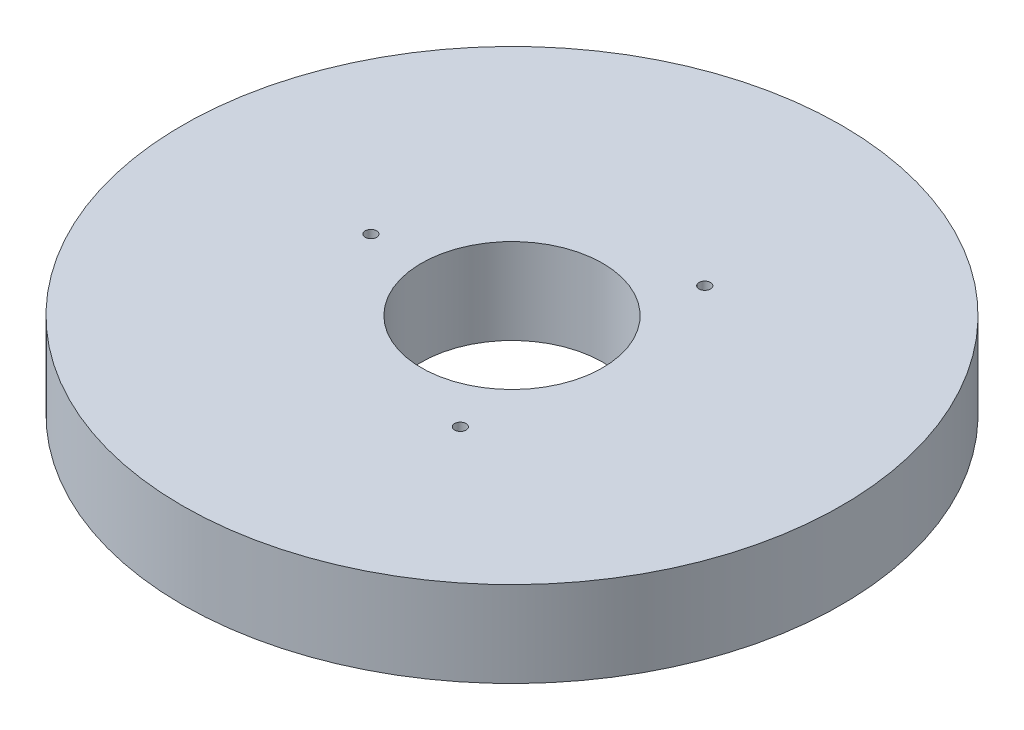
SolidWorks part; units mm, degrees
ref_plane "Front Plane" through (0, 0, 0) normal (0, 0, 1) x (1, 0, 0)
ref_plane "Top Plane" through (0, 0, 0) normal (0, 1, 0) x (1, 0, 0)
ref_plane "Right Plane" through (0, 0, 0) normal (1, 0, 0) x (0, 0, -1)
sketch "Sketch1" plane through (0, 0, 0) normal (0, 1, 0) x (1, 0, 0)
  circle A0 centre (0, 0) radius 100
  dimension "FLANGE_OD" = 200
extrude "Boss-Extrude1" add sketch "Sketch1" along normal blind 26
sketch "Sketch2" plane through (0, 0, 0) normal (0, 1, 0) x (1, 0, 0)
  circle A0 centre (0, 0) radius 27.5
  dimension "BORE_D" = 55
extrude "Cut-Extrude1" cut sketch "Sketch2" along normal through all
sketch "Sketch3" plane through (0, 26, 0) normal (0, 1, 0) x (1, 0, 0)
  circle A0 centre (0, 0) radius 42.8122 construction
  circle A1 centre (-42.8122, 0) radius 1.7364
  dimension "BOLT_D" = 3.4727
  dimension "BOLT_PCD" = 85.6243
extrude "Cut-Extrude2" cut sketch "Sketch3" against normal blind 22.8692
pattern_circular "CirPattern1" count 3 over 360 about axis through (0, 0, 0) along (0, 1, 0) of "Cut-Extrude2"
